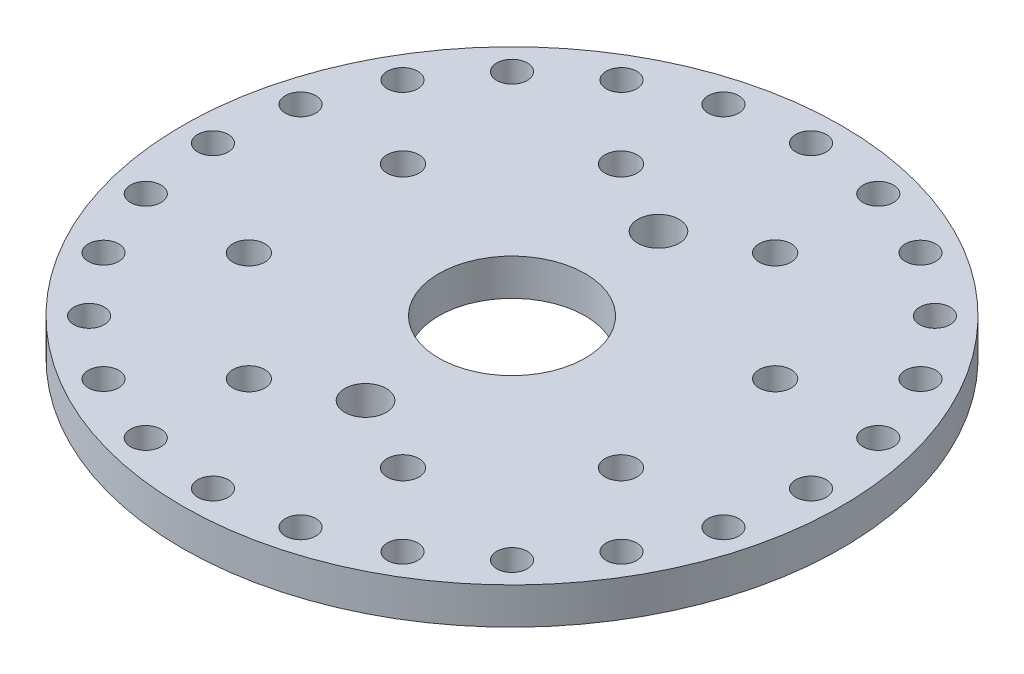
SolidWorks part; units mm, degrees
material "Alloy Steel"
ref_plane "Front Plane" through (0, 0, 0) normal (0, 0, 1) x (1, 0, 0)
ref_plane "Top Plane" through (0, 0, 0) normal (0, 1, 0) x (1, 0, 0)
ref_plane "Right Plane" through (0, 0, 0) normal (1, 0, 0) x (0, 0, -1)
sketch "Sketch5" plane through (0, 0, 0) normal (0, 1, 0) x (1, 0, 0)
  line L0 (87.3464, 51.4964) -> (89.0397, 50.8872)
  line L1 (89.0397, 50.8872) -> (90.7249, 50.062)
  line L2 (90.7249, 50.062) -> (90.7249, 49.095)
  line L3 (90.7249, 49.095) -> (89.0397, 48.2698)
  line L4 (89.0397, 48.2698) -> (87.3464, 47.6606)
  line L5 (87.3464, 47.6606) -> (87.2693, 46.4828)
  line L6 (87.2693, 46.4828) -> (88.8685, 45.6578)
  line L7 (88.8685, 45.6578) -> (90.4317, 44.6196)
  line L8 (90.4317, 44.6196) -> (90.3054, 43.6609)
  line L9 (90.3054, 43.6609) -> (88.5268, 43.0627)
  line L10 (88.5268, 43.0627) -> (86.7686, 42.6797)
  line L11 (86.7686, 42.6797) -> (86.5383, 41.5221)
  line L12 (86.5383, 41.5221) -> (88.0162, 40.4955)
  line L13 (88.0162, 40.4955) -> (89.4304, 39.2621)
  line L14 (89.4304, 39.2621) -> (89.1801, 38.328)
  line L15 (89.1801, 38.328) -> (87.3386, 37.9672)
  line L16 (87.3386, 37.9672) -> (85.5454, 37.8169)
  line L17 (85.5454, 37.8169) -> (85.1661, 36.6994)
  line L18 (85.1661, 36.6994) -> (86.4974, 35.4884)
  line L19 (86.4974, 35.4884) -> (87.7385, 34.0811)
  line L20 (87.7385, 34.0811) -> (87.3685, 33.1877)
  line L21 (87.3685, 33.1877) -> (85.4956, 33.0702)
  line L22 (85.4956, 33.0702) -> (83.6981, 33.1553)
  line L23 (83.6981, 33.1553) -> (83.1762, 32.0968)
  line L24 (83.1762, 32.0968) -> (84.3379, 30.7226)
  line L25 (84.3379, 30.7226) -> (85.3848, 29.1653)
  line L26 (85.3848, 29.1653) -> (84.9013, 28.3278)
  line L27 (84.9013, 28.3278) -> (83.0292, 28.4557)
  line L28 (83.0292, 28.4557) -> (81.2581, 28.7747)
  line L29 (81.2581, 28.7747) -> (80.6024, 27.7935)
  line L30 (80.6024, 27.7935) -> (81.575, 26.2794)
  line L31 (81.575, 26.2794) -> (82.4096, 24.5987)
  line L32 (82.4096, 24.5987) -> (81.821, 23.8315)
  line L33 (81.821, 23.8315) -> (79.9815, 24.2028)
  line L34 (79.9815, 24.2028) -> (78.2673, 24.7502)
  line L35 (78.2673, 24.7502) -> (77.4891, 23.8628)
  line L36 (77.4891, 23.8628) -> (78.2556, 22.2348)
  line L37 (78.2556, 22.2348) -> (78.8638, 20.4595)
  line L38 (78.8638, 20.4595) -> (78.18, 19.7757)
  line L39 (78.18, 19.7757) -> (76.4047, 20.3839)
  line L40 (76.4047, 20.3839) -> (74.7767, 21.1504)
  line L41 (74.7767, 21.1504) -> (73.8893, 20.3722)
  line L42 (73.8893, 20.3722) -> (74.4368, 18.658)
  line L43 (74.4368, 18.658) -> (74.808, 16.8186)
  line L44 (74.808, 16.8186) -> (74.0408, 16.2299)
  line L45 (74.0408, 16.2299) -> (72.3602, 17.0645)
  line L46 (72.3602, 17.0645) -> (70.846, 18.0371)
  line L47 (70.846, 18.0371) -> (69.8648, 17.3814)
  line L48 (69.8648, 17.3814) -> (70.1838, 15.6104)
  line L49 (70.1838, 15.6104) -> (70.3117, 13.7382)
  line L50 (70.3117, 13.7382) -> (69.4742, 13.2547)
  line L51 (69.4742, 13.2547) -> (67.9169, 14.3016)
  line L52 (67.9169, 14.3016) -> (66.5427, 15.4634)
  line L53 (66.5427, 15.4634) -> (65.4842, 14.9415)
  line L54 (65.4842, 14.9415) -> (65.5693, 13.1439)
  line L55 (65.5693, 13.1439) -> (65.4518, 11.271)
  line L56 (65.4518, 11.271) -> (64.5584, 10.901)
  line L57 (64.5584, 10.901) -> (63.1511, 12.1422)
  line L58 (63.1511, 12.1422) -> (61.9401, 13.4734)
  line L59 (61.9401, 13.4734) -> (60.8226, 13.0941)
  line L60 (60.8226, 13.0941) -> (60.6724, 11.3009)
  line L61 (60.6724, 11.3009) -> (60.3115, 9.4594)
  line L62 (60.3115, 9.4594) -> (59.3774, 9.2091)
  line L63 (59.3774, 9.2091) -> (58.144, 10.6233)
  line L64 (58.144, 10.6233) -> (57.1174, 12.1012)
  line L65 (57.1174, 12.1012) -> (55.9598, 11.8709)
  line L66 (55.9598, 11.8709) -> (55.5768, 10.1127)
  line L67 (55.5768, 10.1127) -> (54.9786, 8.3341)
  line L68 (54.9786, 8.3341) -> (54.0199, 8.2078)
  line L69 (54.0199, 8.2078) -> (52.9817, 9.771)
  line L70 (52.9817, 9.771) -> (52.1567, 11.3702)
  line L71 (52.1567, 11.3702) -> (50.979, 11.2931)
  line L72 (50.979, 11.2931) -> (50.3698, 9.5998)
  line L73 (50.3698, 9.5998) -> (49.5446, 7.9146)
  line L74 (49.5446, 7.9146) -> (48.5775, 7.9146)
  line L75 (48.5775, 7.9146) -> (47.7523, 9.5998)
  line L76 (47.7523, 9.5998) -> (47.1431, 11.2931)
  line L77 (47.1431, 11.2931) -> (45.9654, 11.3702)
  line L78 (45.9654, 11.3702) -> (45.1403, 9.771)
  line L79 (45.1403, 9.771) -> (44.1021, 8.2078)
  line L80 (44.1021, 8.2078) -> (43.1434, 8.3341)
  line L81 (43.1434, 8.3341) -> (42.5452, 10.1127)
  line L82 (42.5452, 10.1127) -> (42.1622, 11.8709)
  line L83 (42.1622, 11.8709) -> (41.0046, 12.1012)
  line L84 (41.0046, 12.1012) -> (39.978, 10.6233)
  line L85 (39.978, 10.6233) -> (38.7447, 9.2091)
  line L86 (38.7447, 9.2091) -> (37.8106, 9.4594)
  line L87 (37.8106, 9.4594) -> (37.4497, 11.3009)
  line L88 (37.4497, 11.3009) -> (37.2994, 13.0941)
  line L89 (37.2994, 13.0941) -> (36.1819, 13.4734)
  line L90 (36.1819, 13.4734) -> (34.9709, 12.1422)
  line L91 (34.9709, 12.1422) -> (33.5636, 10.901)
  line L92 (33.5636, 10.901) -> (32.6702, 11.271)
  line L93 (32.6702, 11.271) -> (32.5527, 13.1439)
  line L94 (32.5527, 13.1439) -> (32.6378, 14.9415)
  line L95 (32.6378, 14.9415) -> (31.5793, 15.4634)
  line L96 (31.5793, 15.4634) -> (30.2051, 14.3016)
  line L97 (30.2051, 14.3016) -> (28.6478, 13.2547)
  line L98 (28.6478, 13.2547) -> (27.8103, 13.7382)
  line L99 (27.8103, 13.7382) -> (27.9382, 15.6104)
  line L100 (27.9382, 15.6104) -> (28.2572, 17.3814)
  line L101 (28.2572, 17.3814) -> (27.276, 18.0371)
  line L102 (27.276, 18.0371) -> (25.7619, 17.0645)
  line L103 (25.7619, 17.0645) -> (24.0812, 16.2299)
  line L104 (24.0812, 16.2299) -> (23.314, 16.8186)
  line L105 (23.314, 16.8186) -> (23.6853, 18.658)
  line L106 (23.6853, 18.658) -> (24.2327, 20.3722)
  line L107 (24.2327, 20.3722) -> (23.3453, 21.1504)
  line L108 (23.3453, 21.1504) -> (21.7173, 20.3839)
  line L109 (21.7173, 20.3839) -> (19.9421, 19.7757)
  line L110 (19.9421, 19.7757) -> (19.2582, 20.4595)
  line L111 (19.2582, 20.4595) -> (19.8664, 22.2348)
  line L112 (19.8664, 22.2348) -> (20.6329, 23.8628)
  line L113 (20.6329, 23.8628) -> (19.8547, 24.7502)
  line L114 (19.8547, 24.7502) -> (18.1405, 24.2028)
  line L115 (18.1405, 24.2028) -> (16.3011, 23.8315)
  line L116 (16.3011, 23.8315) -> (15.7124, 24.5987)
  line L117 (15.7124, 24.5987) -> (16.547, 26.2794)
  line L118 (16.547, 26.2794) -> (17.5196, 27.7935)
  line L119 (17.5196, 27.7935) -> (16.8639, 28.7747)
  line L120 (16.8639, 28.7747) -> (15.0929, 28.4557)
  line L121 (15.0929, 28.4557) -> (13.2207, 28.3278)
  line L122 (13.2207, 28.3278) -> (12.7372, 29.1653)
  line L123 (12.7372, 29.1653) -> (13.7841, 30.7226)
  line L124 (13.7841, 30.7226) -> (14.9459, 32.0968)
  line L125 (14.9459, 32.0968) -> (14.424, 33.1553)
  line L126 (14.424, 33.1553) -> (12.6264, 33.0702)
  line L127 (12.6264, 33.0702) -> (10.7535, 33.1877)
  line L128 (10.7535, 33.1877) -> (10.3835, 34.0811)
  line L129 (10.3835, 34.0811) -> (11.6247, 35.4884)
  line L130 (11.6247, 35.4884) -> (12.9559, 36.6994)
  line L131 (12.9559, 36.6994) -> (12.5766, 37.8169)
  line L132 (12.5766, 37.8169) -> (10.7834, 37.9672)
  line L133 (10.7834, 37.9672) -> (8.9419, 38.328)
  line L134 (8.9419, 38.328) -> (8.6916, 39.2621)
  line L135 (8.6916, 39.2621) -> (10.1058, 40.4955)
  line L136 (10.1058, 40.4955) -> (11.5837, 41.5221)
  line L137 (11.5837, 41.5221) -> (11.3534, 42.6797)
  line L138 (11.3534, 42.6797) -> (9.5952, 43.0627)
  line L139 (9.5952, 43.0627) -> (7.8167, 43.6609)
  line L140 (7.8167, 43.6609) -> (7.6903, 44.6196)
  line L141 (7.6903, 44.6196) -> (9.2536, 45.6578)
  line L142 (9.2536, 45.6578) -> (10.8528, 46.4828)
  line L143 (10.8528, 46.4828) -> (10.7757, 47.6606)
  line L144 (10.7757, 47.6606) -> (9.0823, 48.2698)
  line L145 (9.0823, 48.2698) -> (7.3971, 49.095)
  line L146 (7.3971, 49.095) -> (7.3971, 50.062)
  line L147 (7.3971, 50.062) -> (9.0823, 50.8872)
  line L148 (9.0823, 50.8872) -> (10.7757, 51.4964)
  line L149 (10.7757, 51.4964) -> (10.8528, 52.6742)
  line L150 (10.8528, 52.6742) -> (9.2536, 53.4992)
  line L151 (9.2536, 53.4992) -> (7.6903, 54.5374)
  line L152 (7.6903, 54.5374) -> (7.8167, 55.4961)
  line L153 (7.8167, 55.4961) -> (9.5952, 56.0943)
  line L154 (9.5952, 56.0943) -> (11.3534, 56.4773)
  line L155 (11.3534, 56.4773) -> (11.5837, 57.6349)
  line L156 (11.5837, 57.6349) -> (10.1058, 58.6615)
  line L157 (10.1058, 58.6615) -> (8.6916, 59.8949)
  line L158 (8.6916, 59.8949) -> (8.9419, 60.829)
  line L159 (8.9419, 60.829) -> (10.7834, 61.1898)
  line L160 (10.7834, 61.1898) -> (12.5766, 61.3401)
  line L161 (12.5766, 61.3401) -> (12.9559, 62.4576)
  line L162 (12.9559, 62.4576) -> (11.6247, 63.6686)
  line L163 (11.6247, 63.6686) -> (10.3835, 65.0759)
  line L164 (10.3835, 65.0759) -> (10.7535, 65.9693)
  line L165 (10.7535, 65.9693) -> (12.6264, 66.0868)
  line L166 (12.6264, 66.0868) -> (14.424, 66.0017)
  line L167 (14.424, 66.0017) -> (14.9459, 67.0602)
  line L168 (14.9459, 67.0602) -> (13.7841, 68.4344)
  line L169 (13.7841, 68.4344) -> (12.7372, 69.9917)
  line L170 (12.7372, 69.9917) -> (13.2207, 70.8292)
  line L171 (13.2207, 70.8292) -> (15.0929, 70.7013)
  line L172 (15.0929, 70.7013) -> (16.8639, 70.3823)
  line L173 (16.8639, 70.3823) -> (17.5196, 71.3635)
  line L174 (17.5196, 71.3635) -> (16.547, 72.8776)
  line L175 (16.547, 72.8776) -> (15.7124, 74.5583)
  line L176 (15.7124, 74.5583) -> (16.3011, 75.3255)
  line L177 (16.3011, 75.3255) -> (18.1405, 74.9542)
  line L178 (18.1405, 74.9542) -> (19.8547, 74.4068)
  line L179 (19.8547, 74.4068) -> (20.6329, 75.2942)
  line L180 (20.6329, 75.2942) -> (19.8664, 76.9222)
  line L181 (19.8664, 76.9222) -> (19.2582, 78.6975)
  line L182 (19.2582, 78.6975) -> (19.9421, 79.3813)
  line L183 (19.9421, 79.3813) -> (21.7173, 78.7731)
  line L184 (21.7173, 78.7731) -> (23.3453, 78.0066)
  line L185 (23.3453, 78.0066) -> (24.2327, 78.7848)
  line L186 (24.2327, 78.7848) -> (23.6853, 80.499)
  line L187 (23.6853, 80.499) -> (23.314, 82.3384)
  line L188 (23.314, 82.3384) -> (24.0812, 82.9271)
  line L189 (24.0812, 82.9271) -> (25.7619, 82.0925)
  line L190 (25.7619, 82.0925) -> (27.276, 81.1199)
  line L191 (27.276, 81.1199) -> (28.2572, 81.7756)
  line L192 (28.2572, 81.7756) -> (27.9382, 83.5466)
  line L193 (27.9382, 83.5466) -> (27.8103, 85.4188)
  line L194 (27.8103, 85.4188) -> (28.6478, 85.9023)
  line L195 (28.6478, 85.9023) -> (30.2051, 84.8554)
  line L196 (30.2051, 84.8554) -> (31.5793, 83.6936)
  line L197 (31.5793, 83.6936) -> (32.6378, 84.2155)
  line L198 (32.6378, 84.2155) -> (32.5527, 86.0131)
  line L199 (32.5527, 86.0131) -> (32.6702, 87.886)
  line L200 (32.6702, 87.886) -> (33.5636, 88.256)
  line L201 (33.5636, 88.256) -> (34.9709, 87.0148)
  line L202 (34.9709, 87.0148) -> (36.1819, 85.6836)
  line L203 (36.1819, 85.6836) -> (37.2994, 86.0629)
  line L204 (37.2994, 86.0629) -> (37.4497, 87.8561)
  line L205 (37.4497, 87.8561) -> (37.8106, 89.6976)
  line L206 (37.8106, 89.6976) -> (38.7447, 89.9479)
  line L207 (38.7447, 89.9479) -> (39.978, 88.5337)
  line L208 (39.978, 88.5337) -> (41.0046, 87.0558)
  line L209 (41.0046, 87.0558) -> (42.1622, 87.2861)
  line L210 (42.1622, 87.2861) -> (42.5452, 89.0443)
  line L211 (42.5452, 89.0443) -> (43.1434, 90.8228)
  line L212 (43.1434, 90.8228) -> (44.1021, 90.9492)
  line L213 (44.1021, 90.9492) -> (45.1403, 89.386)
  line L214 (45.1403, 89.386) -> (45.9654, 87.7868)
  line L215 (45.9654, 87.7868) -> (47.1431, 87.8639)
  line L216 (47.1431, 87.8639) -> (47.7523, 89.5572)
  line L217 (47.7523, 89.5572) -> (48.5775, 91.2424)
  line L218 (48.5775, 91.2424) -> (49.5446, 91.2424)
  line L219 (49.5446, 91.2424) -> (50.3698, 89.5572)
  line L220 (50.3698, 89.5572) -> (50.979, 87.8639)
  line L221 (50.979, 87.8639) -> (52.1567, 87.7868)
  line L222 (52.1567, 87.7868) -> (52.9817, 89.386)
  line L223 (52.9817, 89.386) -> (54.0199, 90.9492)
  line L224 (54.0199, 90.9492) -> (54.9786, 90.8228)
  line L225 (54.9786, 90.8228) -> (55.5768, 89.0443)
  line L226 (55.5768, 89.0443) -> (55.9598, 87.2861)
  line L227 (55.9598, 87.2861) -> (57.1174, 87.0558)
  line L228 (57.1174, 87.0558) -> (58.144, 88.5337)
  line L229 (58.144, 88.5337) -> (59.3774, 89.9479)
  line L230 (59.3774, 89.9479) -> (60.3115, 89.6976)
  line L231 (60.3115, 89.6976) -> (60.6724, 87.8561)
  line L232 (60.6724, 87.8561) -> (60.8226, 86.0629)
  line L233 (60.8226, 86.0629) -> (61.9401, 85.6836)
  line L234 (61.9401, 85.6836) -> (63.1511, 87.0148)
  line L235 (63.1511, 87.0148) -> (64.5584, 88.256)
  line L236 (64.5584, 88.256) -> (65.4518, 87.886)
  line L237 (65.4518, 87.886) -> (65.5693, 86.0131)
  line L238 (65.5693, 86.0131) -> (65.4842, 84.2155)
  line L239 (65.4842, 84.2155) -> (66.5427, 83.6936)
  line L240 (66.5427, 83.6936) -> (67.9169, 84.8554)
  line L241 (67.9169, 84.8554) -> (69.4742, 85.9023)
  line L242 (69.4742, 85.9023) -> (70.3117, 85.4188)
  line L243 (70.3117, 85.4188) -> (70.1838, 83.5466)
  line L244 (70.1838, 83.5466) -> (69.8648, 81.7756)
  line L245 (69.8648, 81.7756) -> (70.846, 81.1199)
  line L246 (70.846, 81.1199) -> (72.3602, 82.0925)
  line L247 (72.3602, 82.0925) -> (74.0408, 82.9271)
  line L248 (74.0408, 82.9271) -> (74.808, 82.3384)
  line L249 (74.808, 82.3384) -> (74.4368, 80.499)
  line L250 (74.4368, 80.499) -> (73.8893, 78.7848)
  line L251 (73.8893, 78.7848) -> (74.7767, 78.0066)
  line L252 (74.7767, 78.0066) -> (76.4047, 78.7731)
  line L253 (76.4047, 78.7731) -> (78.18, 79.3813)
  line L254 (78.18, 79.3813) -> (78.8638, 78.6975)
  line L255 (78.8638, 78.6975) -> (78.2556, 76.9222)
  line L256 (78.2556, 76.9222) -> (77.4891, 75.2942)
  line L257 (77.4891, 75.2942) -> (78.2673, 74.4068)
  line L258 (78.2673, 74.4068) -> (79.9815, 74.9542)
  line L259 (79.9815, 74.9542) -> (81.821, 75.3255)
  line L260 (81.821, 75.3255) -> (82.4096, 74.5583)
  line L261 (82.4096, 74.5583) -> (81.575, 72.8776)
  line L262 (81.575, 72.8776) -> (80.6024, 71.3635)
  line L263 (80.6024, 71.3635) -> (81.2581, 70.3823)
  line L264 (81.2581, 70.3823) -> (83.0292, 70.7013)
  line L265 (83.0292, 70.7013) -> (84.9013, 70.8292)
  line L266 (84.9013, 70.8292) -> (85.3848, 69.9917)
  line L267 (85.3848, 69.9917) -> (84.3379, 68.4344)
  line L268 (84.3379, 68.4344) -> (83.1762, 67.0602)
  line L269 (83.1762, 67.0602) -> (83.6981, 66.0017)
  line L270 (83.6981, 66.0017) -> (85.4956, 66.0868)
  line L271 (85.4956, 66.0868) -> (87.3685, 65.9693)
  line L272 (87.3685, 65.9693) -> (87.7385, 65.0759)
  line L273 (87.7385, 65.0759) -> (86.4974, 63.6686)
  line L274 (86.4974, 63.6686) -> (85.1661, 62.4576)
  line L275 (85.1661, 62.4576) -> (85.5454, 61.3401)
  line L276 (85.5454, 61.3401) -> (87.3386, 61.1898)
  line L277 (87.3386, 61.1898) -> (89.1801, 60.829)
  line L278 (89.1801, 60.829) -> (89.4304, 59.8949)
  line L279 (89.4304, 59.8949) -> (88.0162, 58.6615)
  line L280 (88.0162, 58.6615) -> (86.5383, 57.6349)
  line L281 (86.5383, 57.6349) -> (86.7686, 56.4773)
  line L282 (86.7686, 56.4773) -> (88.5268, 56.0943)
  line L283 (88.5268, 56.0943) -> (90.3054, 55.4961)
  line L284 (90.3054, 55.4961) -> (90.4317, 54.5374)
  line L285 (90.4317, 54.5374) -> (88.8685, 53.4992)
  line L286 (88.8685, 53.4992) -> (87.2693, 52.6742)
  line L287 (87.2693, 52.6742) -> (87.3464, 51.4964)
  line L288 (49.061, 91.2424) -> (49.061, 7.9146) construction
  line L289 (7.3971, 49.5785) -> (90.7249, 49.5785) construction
  point P292 (49.061, 49.5785)
sketch "Sketch6" plane through (0, 0, 0) normal (0, 1, 0) x (1, 0, 0)
  line L0 (49.061, 91.2424) -> (49.061, 7.9146) construction
  circle A0 centre (49.061, 49.5785) radius 6
  dimension "D1" = 12
sketch "Sketch7" plane through (0, 0, 0) normal (0, 1, 0) x (1, 0, 0)
  line L0 (49.061, 91.2424) -> (49.061, 7.9146) construction
  line L1 (25.4921, 49.5785) -> (64.6594, 49.5785) construction
  line L2 (7.3971, 49.5785) -> (90.7249, 49.5785) construction
  circle A0 centre (49.061, 61.5785) radius 1.7
  circle A1 centre (49.061, 37.5785) radius 1.7
  dimension "D2" = 3.4
  dimension "D1" = 12
sketch "Sketch8" plane through (0, 0, 0) normal (0, 1, 0) x (1, 0, 0)
  line L0 (7.3971, 49.5785) -> (90.7249, 49.5785) construction
  circle A0 centre (49.061, 49.5785) radius 27
  dimension "D1" = 54
sketch "Sketch9" plane through (0, 0, 0) normal (0, 1, 0) x (1, 0, 0)
  line L0 (49.061, 91.2424) -> (49.061, 7.9146) construction
  line L1 (49.061, 74.0785) -> (49.061, 76.5785) construction
  circle A0 centre (49.061, 74.0785) radius 1.25
  circle A1 centre (49.061, 49.5785) radius 27 construction
  circle A2 centre (55.4021, 73.2437) radius 1.25
  circle A3 centre (61.311, 70.7961) radius 1.25
  circle A4 centre (66.3851, 66.9026) radius 1.25
  circle A5 centre (70.2786, 61.8285) radius 1.25
  circle A6 centre (72.7262, 55.9196) radius 1.25
  circle A7 centre (73.561, 49.5785) radius 1.25
  circle A8 centre (72.7262, 43.2374) radius 1.25
  circle A9 centre (70.2786, 37.3285) radius 1.25
  circle A10 centre (66.3851, 32.2544) radius 1.25
  circle A11 centre (61.311, 28.3609) radius 1.25
  circle A12 centre (55.4021, 25.9133) radius 1.25
  circle A13 centre (49.061, 25.0785) radius 1.25
  circle A14 centre (42.7199, 25.9133) radius 1.25
  circle A15 centre (36.811, 28.3609) radius 1.25
  circle A16 centre (31.7369, 32.2544) radius 1.25
  circle A17 centre (27.8434, 37.3285) radius 1.25
  circle A18 centre (25.3958, 43.2374) radius 1.25
  circle A19 centre (24.561, 49.5785) radius 1.25
  circle A20 centre (25.3958, 55.9196) radius 1.25
  circle A21 centre (27.8434, 61.8285) radius 1.25
  circle A22 centre (31.7369, 66.9026) radius 1.25
  circle A23 centre (36.811, 70.7961) radius 1.25
  circle A24 centre (42.7199, 73.2437) radius 1.25
  point P55 (49.061, 49.5785)
  dimension "D1" = 2.5
  dimension "D2" = 2.5
  dimension "D3" = 24
extrude "Boss-Extrude1" add sketch "Sketch8" along normal blind 3
extrude "Boss-Extrude2" [suppressed] add sketch "Sketch5" along normal up to surface (4 mm away)
extrude "Cut-Extrude1" cut sketch "Sketch6" along normal up to next
extrude "Cut-Extrude2" cut sketch "Sketch7" along normal up to next
extrude "Cut-Extrude3" cut sketch "Sketch9" along normal up to next
ref_axis "Axis1" [suppressed] through (49.061, 4, -49.5785) along (0, -1, 0)
sketch "Sketch11" plane through (0, 0, 0) normal (0, 1, 0) x (1, 0, 0)
  line L0 (59.3935, 74.5232) -> (49.061, 49.5785) construction
  line L1 (49.061, 49.5785) -> (49.061, 76.5785) construction
  circle A0 centre (49.061, 49.5785) radius 27 construction
  circle A1 centre (55.3753, 64.8225) radius 1.3125
  circle A2 centre (64.305, 55.8928) radius 1.3125
  circle A3 centre (64.305, 43.2642) radius 1.3125
  circle A4 centre (55.3753, 34.3345) radius 1.3125
  circle A5 centre (42.7467, 34.3345) radius 1.3125
  circle A6 centre (33.817, 43.2642) radius 1.3125
  circle A7 centre (33.817, 55.8928) radius 1.3125
  circle A8 centre (42.7467, 64.8225) radius 1.3125
  point P0 (49.061, 49.5785)
  point P36 (49.061, 49.5785)
  dimension "D2" = 2.625
  dimension "D1" = 16.5
  dimension "D4" = 22.5
  dimension "D3" = 8
extrude "Cut-Extrude4" cut sketch "Sketch11" along normal up to next
